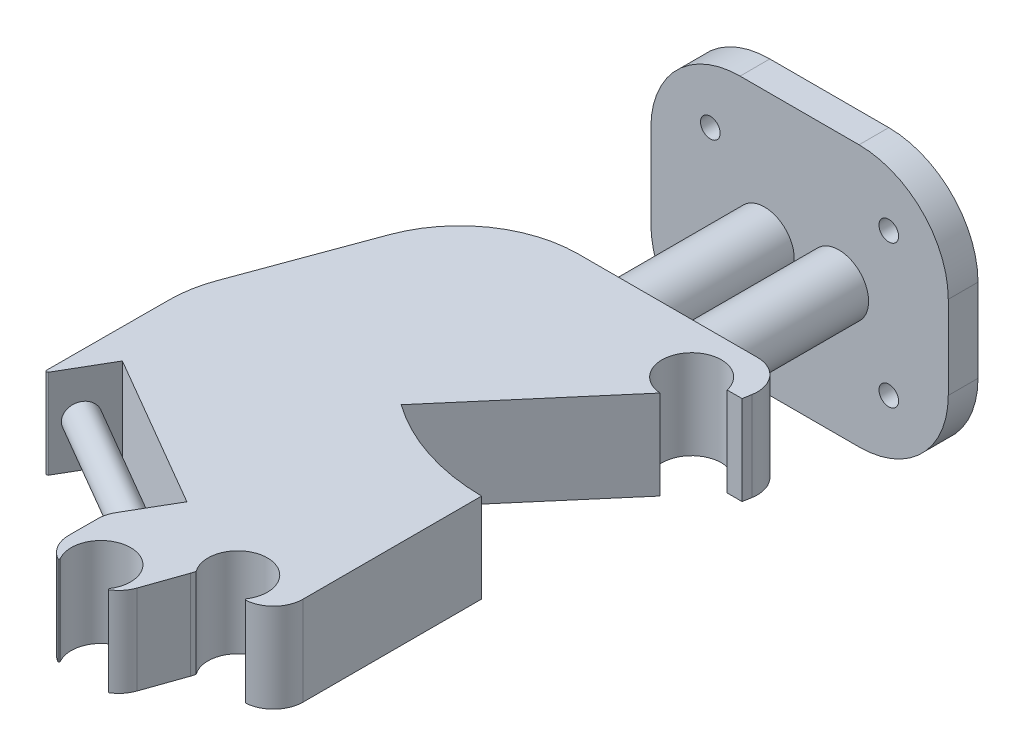
SolidWorks part; units mm, degrees
ref_plane "Front Plane" through (0, 0, 0) normal (0, 0, 1) x (1, 0, 0)
ref_plane "Top Plane" through (0, 0, 0) normal (0, 1, 0) x (1, 0, 0)
ref_plane "Right Plane" through (0, 0, 0) normal (1, 0, 0) x (0, 0, -1)
ref_plane "Plane1" through (0, -7.5, 0) normal (0, 1, 0) x (1, 0, 0)
sketch "Sketch1" plane through (0, -7.5, 0) normal (0, 1, 0) x (1, 0, 0)
  line L0 (-3.3112, 103.3764) -> (-8.3112, 103.3764)
  line L1 (-8.3112, 103.3764) -> (-8.3112, 78.3764)
  line L2 (-8.3112, 78.3764) -> (-3.3112, 78.3764)
  line L3 (-3.3112, 78.3764) -> (-3.3112, 103.3764)
  line L4 (-8.3112, 103.3764) -> (-8.3112, 78.3764) construction
revolve "Revolve1" add sketch "Sketch1" angle 360 about L4 reverse direction yes
ref_plane "Plane2" through (0, -2.5, 0) normal (0, 1, 0) x (1, 0, 0)
sketch "Sketch2" plane through (0, -2.5, 0) normal (0, 1, 0) x (1, 0, 0)
  line L0 (-20.9042, -4.0606) -> (-17.7458, -10)
  line L1 (-15.5719, -7.3481) -> (-13.2352, -0.6719)
  line L2 (0, 5) -> (0, 35)
  line L3 (-20.058, 41.5415) -> (5.1978, 71.09)
  line L4 (5.1978, 71.09) -> (8.9826, 71.09)
  line L5 (8.9826, 71.09) -> (8.9826, 78.3764)
  line L6 (8.9826, 78.3764) -> (-8.3112, 78.3764)
  line L7 (-8.3112, 78.3764) -> (-41.0174, 78.3764)
  line L8 (-41.0174, 78.3764) -> (-54.8193, 40.833)
  line L9 (-54.8193, 40.833) -> (-54.897, 16.7662)
  line L10 (-54.4309, 16.6397) -> (-49.8721, 24.4773)
  line L11 (-49.8721, 24.4773) -> (-8.9678, 0.6849)
  line L12 (-8.9678, 0.6849) -> (-28.9677, 0.7494)
  line L13 (-28.9677, 0.7494) -> (-28.9876, -5.4067)
  line L14 (-26.4535, -9.7725) -> (-20.9042, -4.0606)
  arc A0 (-17.7458, -10) -> (-15.5719, -7.3481) centre (-20.2911, -5.6964) ccw
  arc A1 (-13.2352, -0.6719) -> (-13.0407, 0.0551) centre (-17.9545, 0.9798) ccw
  arc A2 (-13.0407, 0.0551) -> (-5, 0) centre (-9, 3) ccw
  arc A3 (-5, 0) -> (0, 5) centre (-5, 5) ccw
  arc A4 (0, 35) -> (-20.058, 41.5415) centre (0.3184, 69.9986) cw
  arc A5 (-54.897, 16.7662) -> (-54.4309, 16.6397) centre (-54.647, 16.7654) ccw
  arc A6 (-28.9876, -5.4067) -> (-26.4535, -9.7725) centre (-23.9876, -5.4228) ccw
extrude "Boss-Extrude1" add sketch "Sketch2" against normal blind 10
sketch "Sketch3" plane through (0, -12.5, 0) normal (0, -1, 0) x (1, 0, 0)
  line L0 (-20.9042, 4.0606) -> (-17.7458, 10)
  line L1 (-15.5719, 7.3481) -> (-13.2352, 0.6719)
  line L2 (0, -5) -> (0, -35)
  line L3 (-20.058, -41.5415) -> (5.1978, -71.09)
  line L4 (5.1978, -71.09) -> (8.9826, -71.09)
  line L5 (8.9826, -71.09) -> (8.9826, -78.3764)
  line L6 (8.9826, -78.3764) -> (-41.0174, -78.3764)
  line L7 (-41.0174, -78.3764) -> (-54.8193, -40.833)
  line L8 (-54.8193, -40.833) -> (-54.897, -16.7662)
  line L9 (-54.4309, -16.6397) -> (-49.8721, -24.4773)
  line L10 (-49.8721, -24.4773) -> (-8.9678, -0.6849)
  line L11 (-8.9678, -0.6849) -> (-28.9677, -0.7494)
  line L12 (-28.9677, -0.7494) -> (-28.9876, 5.4067)
  line L13 (-26.4535, 9.7725) -> (-20.9042, 4.0606)
  arc A0 (-17.7458, 10) -> (-15.5719, 7.3481) centre (-20.2911, 5.6964) cw
  arc A1 (-13.2352, 0.6719) -> (-13.0407, -0.0551) centre (-17.9545, -0.9798) cw
  arc A2 (-13.0407, -0.0551) -> (-5, 0) centre (-9, -3) cw
  arc A3 (-5, 0) -> (0, -5) centre (-5, -5) cw
  arc A4 (0, -35) -> (-20.058, -41.5415) centre (0.3184, -69.9986) ccw
  arc A5 (-54.897, -16.7662) -> (-54.4309, -16.6397) centre (-54.647, -16.7654) cw
  arc A6 (-28.9876, 5.4067) -> (-26.4535, 9.7725) centre (-23.9876, 5.4228) cw
extrude "Boss-Extrude2" add sketch "Sketch3" along normal blind 2.5
sketch "Sketch4" plane through (0, -2.5, 0) normal (0, 1, 0) x (-1, 0, 0)
  line L0 (20.9042, 4.0606) -> (26.4535, 9.7725)
  line L1 (28.9876, 5.4067) -> (28.9677, -0.7494)
  line L2 (28.9677, -0.7494) -> (8.9678, -0.6849)
  line L3 (8.9678, -0.6849) -> (49.8721, -24.4773)
  line L4 (49.8721, -24.4773) -> (54.4309, -16.6397)
  line L5 (54.897, -16.7662) -> (54.8193, -40.833)
  line L6 (54.8193, -40.833) -> (41.0174, -78.3764)
  line L7 (41.0174, -78.3764) -> (-8.9826, -78.3764)
  line L8 (-8.9826, -78.3764) -> (-8.9826, -71.09)
  line L9 (-8.9826, -71.09) -> (-5.1978, -71.09)
  line L10 (-5.1978, -71.09) -> (20.058, -41.5415)
  line L11 (0, -35) -> (0, -5)
  line L12 (13.2352, 0.6719) -> (15.5719, 7.3481)
  line L13 (17.7458, 10) -> (20.9042, 4.0606)
  arc A0 (26.4535, 9.7725) -> (28.9876, 5.4067) centre (23.9876, 5.4228) cw
  arc A1 (54.4309, -16.6397) -> (54.897, -16.7662) centre (54.647, -16.7654) cw
  arc A2 (20.058, -41.5415) -> (0, -35) centre (-0.3184, -69.9986) ccw
  arc A3 (0, -5) -> (5, 0) centre (5, -5) cw
  arc A4 (5, 0) -> (13.0407, -0.0551) centre (9, -3) cw
  arc A5 (13.0407, -0.0551) -> (13.2352, 0.6719) centre (17.9545, -0.9798) cw
  arc A6 (15.5719, 7.3481) -> (17.7458, 10) centre (20.2911, 5.6964) cw
extrude "Boss-Extrude3" add sketch "Sketch4" along normal blind 2.5
ref_plane "Plane3" through (0, 0, -103.3764) normal (0, 0, 1) x (1, 0, 0)
sketch "Sketch5" plane through (0, 0, -103.3764) normal (0, 0, 1) x (1, 0, 0)
  line L0 (-39.9176, -7.5) -> (10.0824, -7.5) construction
  line L1 (-39.9176, -29.5) -> (10.0824, -29.5)
  line L2 (-39.9176, -29.5) -> (-39.9176, 14.5)
  line L3 (-39.9176, 14.5) -> (10.0824, 14.5)
  line L4 (10.0824, -29.5) -> (10.0824, 14.5)
  line L5 (-13.3112, -7.5) -> (-3.3112, -7.5) construction
  line L6 (55, -7.5) -> (-55, -7.5) construction
  line L7 (-8.3112, -12.5) -> (-8.3112, -2.5) construction
  line L9 (5.5, -2.5) -> (-5.5, -2.5) construction
  line L10 (0.0824, -19.5) -> (0.0824, 4.5) construction
  line L11 (-29.9176, -19.5) -> (-29.9176, 4.5) construction
  circle A0 centre (-29.9176, -19.5) radius 1.65
  circle A1 centre (0.0824, -19.5) radius 1.65
  circle A2 centre (0.0824, 4.5) radius 1.65
  circle A3 centre (-29.9176, 4.5) radius 1.65
  circle A4 centre (-8.3112, -7.5) radius 5 construction
  circle A6 centre (-8.3112, -7.5) radius 5 construction
  point P27 (-8.3112, -12.5)
  dimension "D9" = 3.3
  dimension "D10" = 3.3
  dimension "D11" = 3.3
  dimension "D12" = 3.3
  dimension "D1" = 50
  dimension "D2" = 44
  dimension "D3" = 30
  dimension "D4" = 10
  dimension "D5" = 30
  dimension "D6" = 10
  dimension "D7" = 24
  dimension "D8" = 10
  dimension "D13" = 10
  dimension "D14" = 24
  dimension "D15" = 0
extrude "Boss-Extrude4" add sketch "Sketch5" against normal blind 5
draft "Draft1" type of draft neutral plane draft angle 60 faces to draft 1 face at (-18.9678, -7.5, -0.7172) neutral plane through (-28.9677, -12.5, -0.7494) neutral plane normal (-1, 0, -0.0032) parameters "D1"=60
draft "Draft2" type of draft neutral plane draft angle 10 faces to draft 1 face at (8.9826, -7.5, -74.7332) neutral plane through (-8.3112, -12.5, -78.3764) neutral plane normal (0, 0, -1) reverse direction yes parameters "D1"=10
ref_plane "Plane4" through (0, 0, 7) normal (0, 0, 1) x (1, 0, 0)
sketch "Sketch6" plane through (0, 0, 7) normal (0, 0, 1) x (1, 0, 0)
  line L0 (-17, 0) -> (-22, 0)
  line L1 (-22, 0) -> (-22, -15)
  line L2 (-22, -15) -> (-17, -15)
  line L3 (-17, -15) -> (-17, 0)
  line L4 (-22, 0) -> (-22, -15) construction
revolve "Cut-Revolve1" cut sketch "Sketch6" angle 360 about L4 reverse direction yes
ref_plane "Plane5" through (0, 0, -3) normal (0, 0, -1) x (-1, 0, 0)
sketch "Sketch7" plane through (0, 0, -3) normal (0, 0, -1) x (-1, 0, 0)
  line L0 (4, -15) -> (9, -15)
  line L1 (9, -15) -> (9, 0)
  line L2 (9, 0) -> (4, 0)
  line L3 (4, 0) -> (4, -15)
  line L4 (9, -15) -> (9, 0) construction
revolve "Cut-Revolve2" cut sketch "Sketch7" angle 360 about L4 reverse direction yes
sketch "Sketch8" plane through (0, -7.5, 0) normal (0, 1, 0) x (1, 0, 0)
  line L0 (-15.8112, 103.3764) -> (-20.8112, 103.3764)
  line L1 (-20.8112, 103.3764) -> (-20.8112, 78.3764)
  line L2 (-20.8112, 78.3764) -> (-15.8112, 78.3764)
  line L3 (-15.8112, 78.3764) -> (-15.8112, 103.3764)
  line L4 (-20.8112, 103.3764) -> (-20.8112, 78.3764) construction
revolve "Revolve2" add sketch "Sketch8" angle 360 about L4 reverse direction yes
sketch "Sketch9" plane through (0, -7.5, 0) normal (0, 1, 0) x (1, 0, 0)
  line L0 (-51.1291, 22.3162) -> (-52.386, 20.1552)
  line L1 (-52.386, 20.1552) -> (-26.4538, 5.0715)
  line L2 (-26.4538, 5.0715) -> (-25.1968, 7.2325)
  line L3 (-25.1968, 7.2325) -> (-51.1291, 22.3162)
  line L4 (-53.3252, 20.7015) -> (-25.5146, 4.5252) construction
revolve "Revolve3" add sketch "Sketch9" angle 360 about L4 reverse direction yes
hole_wizard "Ø10.0 (10) Diameter Hole1" positions "Sketch11" profile "Sketch10" hole size "Ø10.0" standard "ANSI Metric"
sketch "Sketch11" plane through (0, -15, 0) normal (0, -1, 0) x (-1, 0, 0)
  point P0 (-0.3184, 69.9986)
sketch "Sketch10" plane through (0.3184, -15, -69.9986) normal (1, 0, 0) x (0, 0, -1)
  line L0 (0, 0) -> (0, 29.5)
  line L1 (0, 29.5) -> (5, 29.5)
  line L2 (5, 29.5) -> (5, 0)
  line L5 (5, 0) -> (0, 0)
  line L11 (0, -6.35) -> (0, 107.95) construction
  dimension "Thru Hole Dia." = 10
  dimension "Thru Hole Depth" = 29.5
chamfer "Chamfer1" distance 0.2628 angle 63.474 1 edges at (-5, -7.5, 0) first distance on face at (-1.9822, -7.5, -1.9822)
fillet "Fillet1" radius 5 2 edges at (8.9826, -7.5, -78.3764) (-28.9677, -7.5, -0.7494) tangent propagation no
fillet "Fillet2" radius 20 2 edges at (-41.0174, -7.5, -78.3764) (-54.8193, -7.5, -40.833) tangent propagation no
fillet "Fillet3" radius 15 4 edges at (-39.9176, -29.5, -105.8764) (10.0824, -29.5, -105.8764) (-39.9176, 14.5, -105.8764) (10.0824, 14.5, -105.8764)
